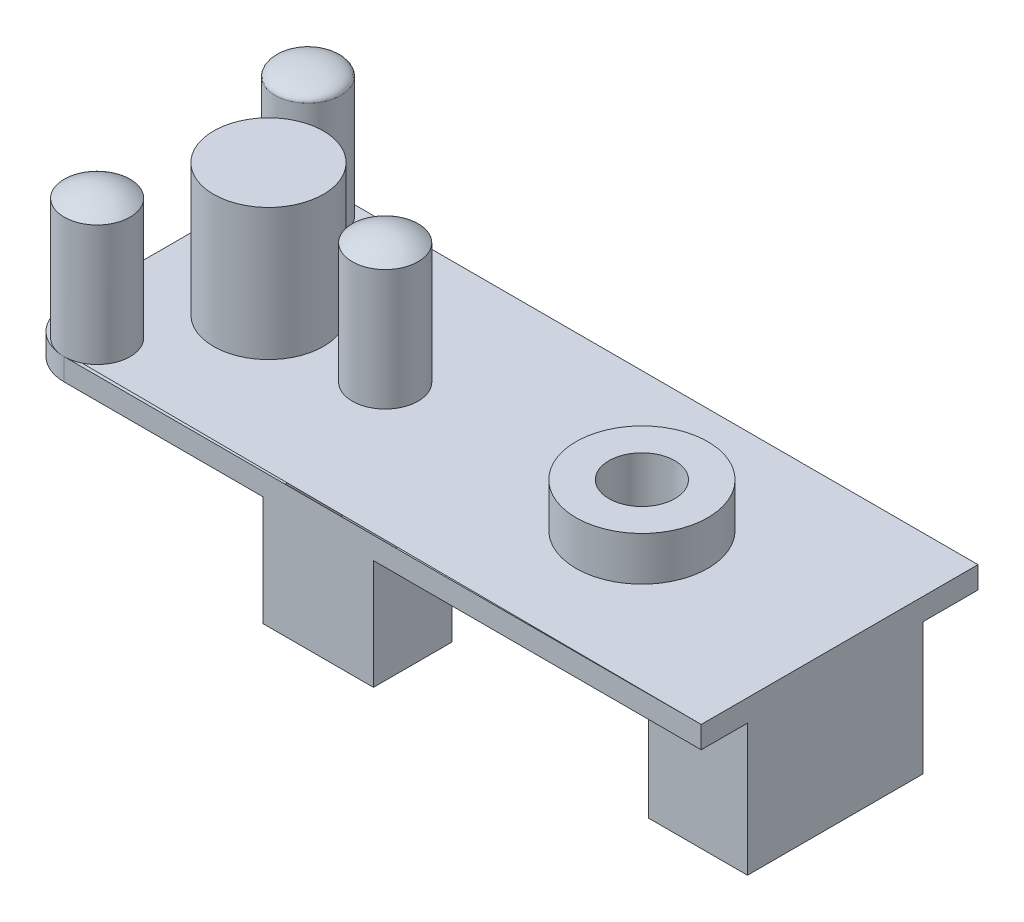
SolidWorks part; units mm, degrees
ref_plane "前视基准面" through (0, 0, 0) normal (0, 0, 1) x (1, 0, 0)
ref_plane "上视基准面" through (0, 0, 0) normal (0, 1, 0) x (1, 0, 0)
ref_plane "右视基准面" through (0, 0, 0) normal (1, 0, 0) x (0, 0, -1)
sketch "草图1" plane through (0, 0, 0) normal (0, 1, 0) x (1, 0, 0)
  line L1 (-15.5, 6.3) -> (15.5, 6.3)
  line L2 (-15.5, 6.3) -> (-15.5, -6.3)
  line L3 (-15.5, -6.3) -> (15.5, -6.3)
  line L4 (15.5, 6.3) -> (15.5, -6.3)
  line L5 (-15.5, 6.3) -> (15.5, -6.3) construction
  line L6 (-15.5, -6.3) -> (15.5, 6.3) construction
  point P0 (0, 0)
  dimension "D1" = 31
  dimension "D2" = 12.6
extrude "凸台-拉伸1" add sketch "草图1" along normal blind 1
sketch "草图2" plane through (0, 1, 0) normal (0, 1, 0) x (1, 0, 0)
  line L0 (-15.5, 0) -> (15.5, 0) construction
  line L1 (-15.5, 6.3) -> (-15.5, -6.3) construction
  line L2 (15.5, -6.3) -> (15.5, 6.3) construction
  circle A0 centre (-10.5, 0) radius 2.5
  dimension "D1" = 5
extrude "凸台-拉伸2" add sketch "草图2" along normal blind 6
sketch "草图3" plane through (0, 1, 0) normal (0, 1, 0) x (1, 0, 0)
  line L0 (-15.5, -6.3) -> (15.5, -6.3) construction
  line L1 (-15.5, 6.3) -> (-15.5, -6.3) construction
  line L2 (-15.5, 0) -> (15.5, 0) construction
  line L3 (15.5, -6.3) -> (15.5, 6.3) construction
  circle A0 centre (-13.5, -4.8) radius 1.5
  circle A1 centre (-13.5, 4.8) radius 1.5
  circle A2 centre (-5.1862, 0) radius 1.5
  dimension "D1" = 1.5
  dimension "D2" = 2
  dimension "D3" = 9.6
extrude "凸台-拉伸3" add sketch "草图3" along normal blind 5.5
dome "圆顶1" faces to dome 1 distance 0.5 reverse direction no elliptical dome yes face at (-13.5, 6.5, -6.3) parameters "D1"=0.5
dome "圆顶2" faces to dome 1 distance 0.5 reverse direction no elliptical dome no face at (-13.5, 6.5, 6.3) parameters "D1"=0.5
dome "圆顶3" faces to dome 1 distance 0.5 reverse direction no elliptical dome no face at (-5.1862, 6.5, 1.5) parameters "D1"=0.5
sketch "草图4" plane through (0, 1, 0) normal (0, 1, 0) x (1, 0, 0)
  line L0 (-15.5, 6.3) -> (-15.5, -6.3) construction
  circle A0 centre (6.5, 0) radius 1.5
  dimension "D1" = 22
extrude "切除-拉伸1" cut sketch "草图4" against normal through all
sketch "草图5" plane through (0, 1, 0) normal (0, 1, 0) x (1, 0, 0)
  circle A0 centre (6.5, 0) radius 3
  circle A1 centre (6.5, 0) radius 1.5
extrude "凸台-拉伸4" add sketch "草图5" along normal blind 2
sketch "草图6" plane through (0, 0, 0) normal (0, -1, 0) x (-1, 0, 0)
  line L0 (15.5, 0) -> (-15.5, 0) construction
  line L1 (15.5, 6.3) -> (15.5, -6.3) construction
  line L2 (-15.5, -6.3) -> (-15.5, 6.3) construction
  line L10 (-15.5, 3.8066) -> (-15.5, -4.1934)
  line L11 (-11, 3.8066) -> (-15.5, 3.8066)
  line L12 (-11, -4.1934) -> (-11, 3.8066)
  line L13 (-15.5, -4.1934) -> (-11, -4.1934)
  dimension "D1" = 0
  dimension "D2" = 4.5
  dimension "D3" = 8
  dimension "D4" = 90
  dimension "D5" = 90
  dimension "D6" = 90
extrude "凸台-拉伸6" add sketch "草图6" along normal blind 6
sketch "草图7" plane through (0, -6, 0) normal (0, -1, 0) x (1, 0, 0)
  line L0 (13.25, 4.1934) -> (13.25, -3.8066) construction
  line L1 (15.5, 4.1934) -> (11, 4.1934) construction
  line L2 (11, -3.8066) -> (15.5, -3.8066) construction
  line L4 (11.5584, 3.4427) -> (14.9416, 3.4427)
  line L5 (11.5584, 3.4427) -> (11.5584, -3.0558)
  line L6 (11.5584, -3.0558) -> (14.9416, -3.0558)
  line L7 (14.9416, 3.4427) -> (14.9416, -3.0558)
  line L8 (11.5584, 3.4427) -> (14.9416, -3.0558) construction
  line L9 (11.5584, -3.0558) -> (14.9416, 3.4427) construction
  point P6 (13.25, 0.1934)
extrude "切除-拉伸2" cut sketch "草图7" against normal blind 5
fillet "圆角1" radius 2 2 edges at (-15.5, 0.5, -6.3) (-15.5, 0.5, 6.3)
sketch "草图9" plane through (0, 0, 0) normal (0, -1, 0) x (1, 0, 0)
  line L0 (-13.5, 6.3) -> (15.5, 6.3) construction
  line L1 (-4.4402, 6.3) -> (0.5792, 6.3)
  line L2 (-4.4402, 6.3) -> (-4.4402, 2.7188)
  line L3 (-4.4402, 2.7188) -> (0.5792, 2.7188)
  line L4 (0.5792, 6.3) -> (0.5792, 2.7188)
extrude "凸台-拉伸7" add sketch "草图9" along normal blind 5
